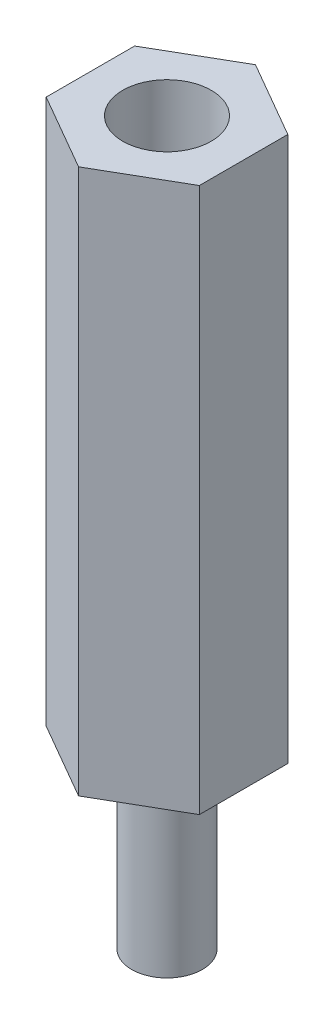
SolidWorks part; units mm, degrees
ref_plane "Front Plane" through (0, 0, 0) normal (0, 0, 1) x (1, 0, 0)
ref_plane "Top Plane" through (0, 0, 0) normal (0, 1, 0) x (1, 0, 0)
ref_plane "Right Plane" through (0, 0, 0) normal (1, 0, 0) x (0, 0, -1)
sketch "Sketch1" plane through (0, 0, 0) normal (0, 1, 0) x (1, 0, 0)
  line L1 (0, 2.5) -> (-2.1651, 1.25)
  line L2 (-2.1651, 1.25) -> (-2.1651, -1.25)
  line L3 (-2.1651, -1.25) -> (0, -2.5)
  line L4 (0, -2.5) -> (2.1651, -1.25)
  line L5 (2.1651, -1.25) -> (2.1651, 1.25)
  line L6 (2.1651, 1.25) -> (0, 2.5)
  circle A0 centre (0, 0) radius 2.5 construction
  circle A1 centre (0, 0) radius 1.25
  dimension "D1" = 5
  dimension "D2" = 2.5
extrude "Body" add sketch "Sketch1" along normal blind 14.4
sketch "Sketch2" plane through (0, 0, 0) normal (0, -1, 0) x (1, 0, 0)
  line L6 (0, -2.5) -> (2.1651, -1.25)
  line L7 (2.1651, -1.25) -> (2.1651, 1.25)
  line L8 (2.1651, 1.25) -> (0, 2.5)
  line L9 (0, 2.5) -> (-2.1651, 1.25)
  line L10 (-2.1651, 1.25) -> (-2.1651, -1.25)
  line L11 (-2.1651, -1.25) -> (0, -2.5)
  line L12 (0, -2.5) -> (2.1651, -1.25)
  line L13 (2.1651, -1.25) -> (2.1651, 1.25)
  line L14 (2.1651, 1.25) -> (0, 2.5)
  line L15 (0, 2.5) -> (-2.1651, 1.25)
  line L16 (-2.1651, 1.25) -> (-2.1651, -1.25)
  line L17 (-2.1651, -1.25) -> (0, -2.5)
  dimension "D1" = 0
extrude "End" add sketch "Sketch2" along normal blind 1
sketch "Sketch3" plane through (0, -1, 0) normal (0, -1, 0) x (1, 0, 0)
  circle A0 centre (0, 0) radius 1
  dimension "D1" = 2
extrude "Screw" add sketch "Sketch3" along normal blind 5
